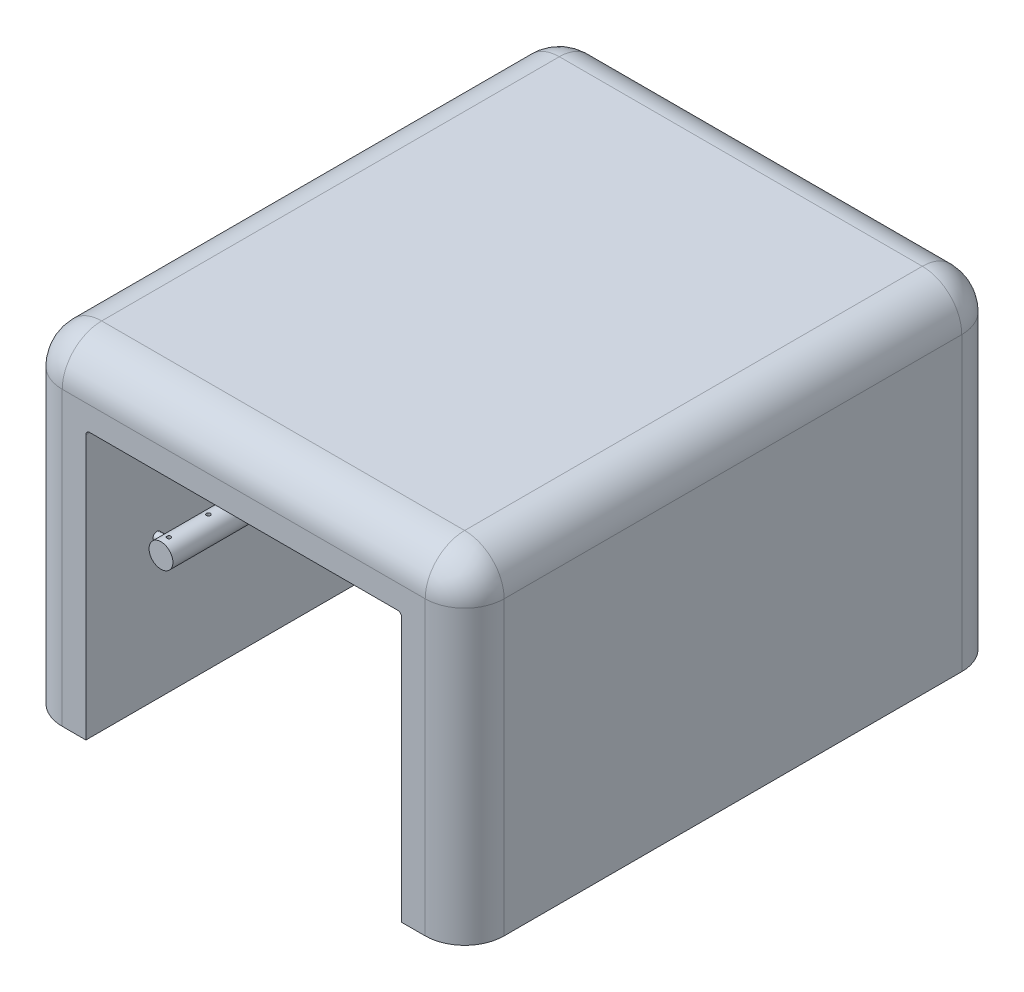
SolidWorks part; units mm, degrees
ref_plane "Front Plane" through (0, 0, 0) normal (0, 0, 1) x (1, 0, 0)
ref_plane "Top Plane" through (0, 0, 0) normal (0, 1, 0) x (1, 0, 0)
ref_plane "Right Plane" through (0, 0, 0) normal (1, 0, 0) x (0, 0, -1)
sketch "Sketch1" plane through (0, 0, 0) normal (1, 0, 0) x (0, 0, -1)
  line L1 (0, 0) -> (680, 0)
  line L2 (0, 0) -> (0, 420)
  line L3 (0, 420) -> (680, 420)
  line L4 (680, 0) -> (680, 420)
  dimension "D1" = 420
  dimension "D2" = 680
extrude "Boss-Extrude1" add sketch "Sketch1" along normal blind 560
sketch "Sketch4" plane through (0, 0, 0) normal (0, 0, 1) x (1, 0, 0)
  line L0 (560, 0) -> (0, 0) construction
  line L1 (80, 0) -> (480, 0)
  line L2 (80, 0) -> (80, 340)
  line L3 (80, 340) -> (480, 340)
  line L4 (480, 0) -> (480, 340)
  line L5 (560, 420) -> (560, 0) construction
  line L6 (560, 420) -> (0, 420) construction
  line L7 (0, 420) -> (0, 0) construction
  dimension "D1" = 80
  dimension "D2" = 80
  dimension "D3" = 80
extrude "Cut-Extrude1" cut sketch "Sketch4" against normal offset from surface (560 mm away) 120 up to face at (280, 210, -680)
ref_plane "Plane1" through (80, 0, 0) normal (1, 0, 0) x (0, 0, -1)
sketch "Sketch6" plane through (80, 0, 0) normal (1, 0, 0) x (0, 0, -1)
  line L0 (560, 160) -> (600, 80)
  line L1 (600, 80) -> (560, 80)
  line L2 (560, 80) -> (560, 160)
  line L3 (680, 0) -> (680, 420) construction
  line L4 (0, 0) -> (680, 0) construction
  dimension "D1" = 80
  dimension "D2" = 120
  dimension "D3" = 80
  dimension "D4" = 80
extrude "Cut-Extrude2" cut sketch "Sketch6" along normal up to surface (400 mm away) up to face at (480, 170, -280)
sketch "Sketch7" plane through (0, 0, -560) normal (0, 0, 1) x (1, 0, 0)
  line L2 (480, 160) -> (80, 160) construction
  line L3 (80, 160) -> (80, 340) construction
  circle A0 centre (105.125, 180.125) radius 15.125
  point P7 (280, 340)
  dimension "D1" = 30.25
  dimension "D2" = 5
  dimension "D3" = 10
extrude "Boss-Extrude2" add sketch "Sketch7" along normal offset from surface (490 mm away) 70 up to face at (280, 190, 0)
ref_plane "Plane2" through (0, 195.25, 0) normal (0, 1, 0) x (1, 0, 0)
ref_plane "Plane3" through (0, 0, -74) normal (0, 0, 1) x (1, 0, 0)
sketch "Sketch10" plane through (0, 0, -70) normal (0, 0, 1) x (1, 0, 0)
  circle A0 centre (105.125, 180.125) radius 11.125
  circle A1 centre (105.125, 180.125) radius 15.125 construction
  dimension "D1" = 4
extrude "Cut-Extrude3" cut sketch "Sketch10" against normal up to surface (490 mm away) from surface up to face at (120.25, 180.125, -560) starting at plane "Plane3"
sketch "Sketch9" plane through (0, 195.25, 0) normal (0, 1, 0) x (1, 0, 0)
  line L0 (90, 530) -> (120.25, 530) construction
  line L1 (90, 560) -> (90, 70) construction
  line L2 (120.25, 70) -> (120.25, 560) construction
  line L3 (80, 560) -> (480, 560) construction
  circle A0 centre (105.125, 530) radius 2.5
  circle A1 centre (105.125, 480) radius 2.5
  circle A2 centre (105.125, 430) radius 2.5
  circle A3 centre (105.125, 380) radius 2.5
  circle A4 centre (105.125, 330) radius 2.5
  circle A5 centre (105.125, 280) radius 2.5
  circle A6 centre (105.125, 230) radius 2.5
  circle A7 centre (105.125, 180) radius 2.5
  circle A8 centre (105.125, 130) radius 2.5
  circle A9 centre (105.125, 80) radius 2.5
  point P10 (105.125, 530)
  dimension "D1" = 5
  dimension "D2" = 30
  dimension "D3" = 10
extrude "Cut-Extrude4" cut sketch "Sketch9" against normal up to next
ref_axis "Axis1" through (280, 340, -560) along (0, -1, 0)
ref_plane "Plane4" through (280, 0, 0) normal (1, 0, 0) x (0, 0, -1)
sketch "Sketch11" plane through (80, 0, 0) normal (1, 0, 0) x (0, 0, -1)
  line L0 (70, 195.25) -> (70, 165) construction
  circle A0 centre (90, 179) radius 5
  dimension "D2" = 10
  dimension "D1" = 20
  dimension "D3" = 19
extrude "Boss-Extrude3" add sketch "Sketch11" along normal up to next
mirror "Mirror1" about plane through (280, 0, 0) normal (1, 0, 0) of "Boss-Extrude3", "Cut-Extrude3", "Cut-Extrude4", "Boss-Extrude2"
fillet "Fillet2" radius 50 8 edges at (280, 420, -680) (560, 420, -340) (280, 420, 0) (0, 420, -340) (0, 210, 0) (560, 210, 0) (560, 210, -680) (0, 210, -680)
fillet "Fillet3" radius 5 14 edges at (480, 40, -560) (80, 40, -560) (480, 120, -580) (80, 120, -580) (480, 80, -580) (80, 80, -580) (280, 80, -560) (280, 80, -600) (280, 160, -560) (480, 340, -280) (480, 250, -560) (280, 340, -560) (80, 250, -560) (80, 340, -280)
